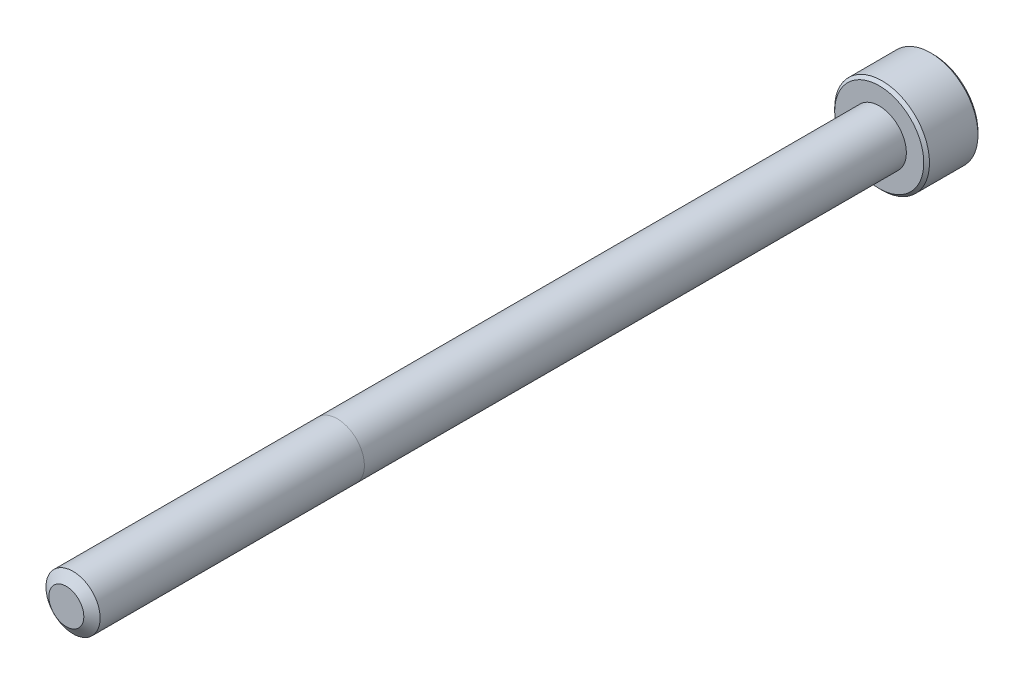
SolidWorks part; units mm, degrees
material "Alloy Steel"
ref_plane "Front Plane" through (0, 0, 0) normal (0, 0, 1) x (1, 0, 0)
ref_plane "Top Plane" through (0, 0, 0) normal (0, 1, 0) x (1, 0, 0)
ref_plane "Right Plane" through (0, 0, 0) normal (1, 0, 0) x (0, 0, -1)
sketch "Sketch1" plane through (0, 0, 0) normal (0, 0, 1) x (1, 0, 0)
  circle A0 centre (0, 0) radius 2
  dimension "OD" = 4
extrude "Extrude1" add sketch "Sketch1" against normal blind 60
sketch "Sketch2" plane through (0, 0, 0) normal (0, 0, 1) x (1, 0, 0)
  circle A0 centre (0, 0) radius 2 construction
  circle A1 centre (0, 0) radius 2
curve "Helix/Spiral1" pitch 0.7 height 60.7 turns 86.7143 parameters "pitch"=0.7
sketch "Sketch3" plane through (0, 0, 0) normal (1, 0, 0) x (0, 0, -1)
  line L0 (-0.6125, 2) -> (-0.35, 1.5453)
  line L1 (-0.35, 1.5453) -> (-0.2625, 1.5453)
  line L2 (-0.2625, 1.5453) -> (0, 2)
  line L3 (-0.6125, 2) -> (0, 2)
  line L4 (-0.3062, 2) -> (-0.3062, 1.5453) construction
  line L5 (-0.4812, 1.7727) -> (-0.1312, 1.7727) construction
  line L6 (0, 2) -> (0, -2) construction
  line L7 (0, -2) -> (60, -2) construction
  point P11 (3.15, -2)
  dimension "D1" = 0.0875
  dimension "D2" = 0.35
  dimension "D3" = 60
  dimension "D4" = 3.15
sweep "Cut-Sweep1" [suppressed] cut profiles "Sketch3" path "Helix/Spiral1"
sketch "Sketch4" plane through (0, 0, 0) normal (1, 0, 0) x (0, 0, -1)
  line L0 (0.4962, 2) -> (0, 1.2913)
  line L1 (0, 1.2913) -> (0, 2)
  line L2 (0.4962, 2) -> (0, 2)
  line L3 (-0.6125, 2) -> (0, 2) construction
  line L4 (0, 0) -> (7.0209, 0) construction
  dimension "D1" = 55
  dimension "D2" = 0.254
revolve "Cut-Revolve1" cut sketch "Sketch4" angle 360 about L4
sketch "Sketch5" [suppressed] plane through (0, 0, 0) normal (1, 0, 0) x (0, 0, -1)
  line L0 (60, -1.9002) -> (60, 0.3311) construction
  line L1 (60, 2) -> (20.1202, 2)
  line L2 (60, 2) -> (60, 0)
  line L3 (60, 0) -> (20, 0)
  line L4 (20, 1.6698) -> (20, 0)
  line L5 (20.1202, 2) -> (20, 1.6698)
  line L6 (0, 0) -> (9.9695, 0) construction
  point P3 (20, 2)
  point P10 (20, 2)
  dimension "D1" = 0.3302
  dimension "Thread min" = 20
  dimension "D3" = 20
revolve "partially thread" [suppressed] add sketch "Sketch5" angle 360 about L6
sketch "Sketch6" plane through (0, 0, -60) normal (0, 0, -1) x (-1, 0, 0)
  circle A0 centre (0, 0) radius 3.5
  dimension "head dia" = 7
extrude "Extrude2" add sketch "Sketch6" along normal blind 4
sketch "Sketch7" plane through (0, 0, -64) normal (0, 0, -1) x (-1, 0, 0)
  line L1 (0, 1.7321) -> (-1.5, 0.866)
  line L2 (-1.5, 0.866) -> (-1.5, -0.866)
  line L3 (-1.5, -0.866) -> (0, -1.7321)
  line L4 (0, -1.7321) -> (1.5, -0.866)
  line L5 (1.5, -0.866) -> (1.5, 0.866)
  line L6 (1.5, 0.866) -> (0, 1.7321)
  circle A0 centre (0, 0) radius 1.5 construction
  dimension "hex dia" = 3
extrude "Cut-Extrude1" cut sketch "Sketch7" against normal blind 2.25
sketch "Sketch8" plane through (0, 0, -64) normal (0, 0, -1) x (-1, 0, 0)
  circle A0 centre (0, 0) radius 1.7321
extrude "Cut-Extrude2" cut sketch "Sketch8" against normal through all draft 45
chamfer "Chamfer1" distance 0.21 angle 45 2 edges at (-3.5, 0, -64) (-3.5, 0, -60)
sketch "Sketch9" plane through (0, 0, 0) normal (1, 0, 0) x (0, 0, -1)
  line L0 (0, 2) -> (0, -2) construction
  line L1 (3.85, 2) -> (3.85, -2) construction
  dimension "D1" = 3.85
sketch "Sketch10" plane through (0, 0, 0) normal (1, 0, 0) x (0, 0, -1)
  line L0 (60, 2) -> (60, 0)
  line L1 (60, 2) -> (59.825, 2)
  line L2 (59.825, 2) -> (58.9966, 0)
  line L3 (60, 0) -> (58.9966, 0)
  line L4 (60, 3.29) -> (60, -3.29) construction
  dimension "D1" = 22.5
  dimension "D2" = 0.175
revolve "Revolve1" add sketch "Sketch10" angle 360 about L3
sketch "Sketch11" plane through (0, 0, 0) normal (1, 0, 0) x (0, 0, -1)
  line L0 (20, 6.6862) -> (20, -5.7877)
  line L1 (0, 3.85) -> (0, -3.85) construction
  dimension "D1" = 20
split line "Split Line1"
equation "\"D3@Helix/Spiral1\" = \"screw length@Extrude1\"+\"pitch@Helix/Spiral1\""
equation "\"D1@Sketch3\" = \"pitch@Helix/Spiral1\"*.125"
equation "\"D2@Sketch3\" = \"pitch@Helix/Spiral1\"*.5"
equation "\"D1@Cut-Extrude1\" = \"hex dia@Sketch7\"*.75"
equation "\"D1@Chamfer1\" = \"head dia@Sketch6\"*.03"
equation "\"D1@Sketch9\" = \"pitch@Helix/Spiral1\"*5.5"
equation "\"D2@Sketch10\" = \"pitch@Helix/Spiral1\"*.25"
equation "\"D4@Sketch3\" = \"pitch@Helix/Spiral1\"*4.50"
